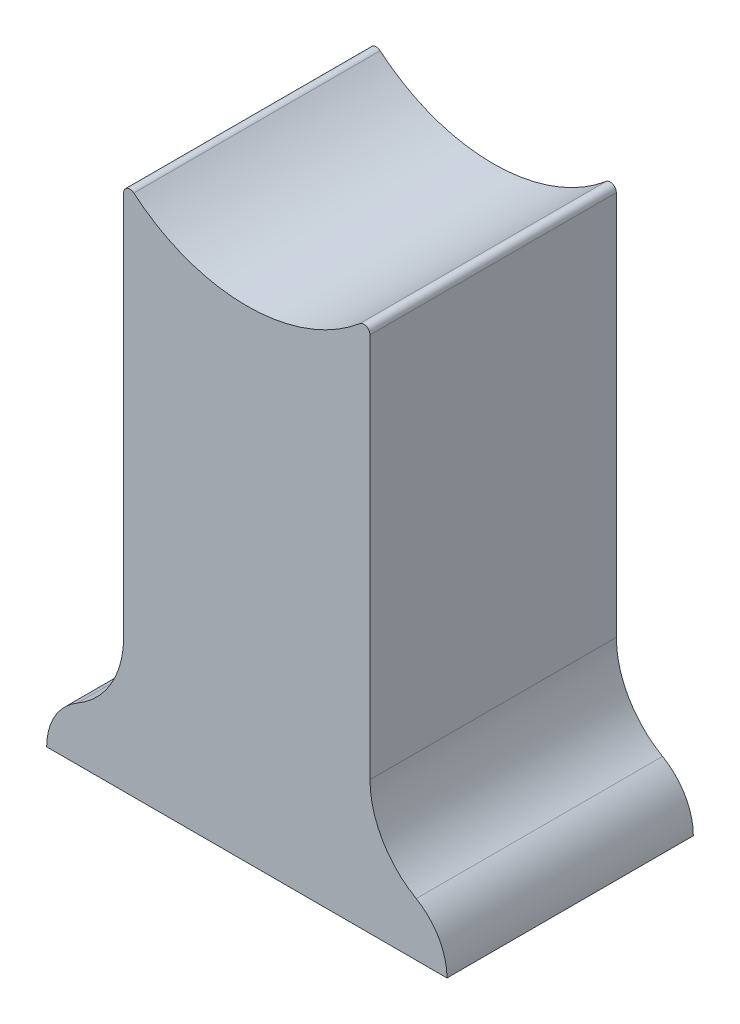
SolidWorks part; units mm, degrees
ref_plane "前视基准面" through (0, 0, 0) normal (0, 0, 1) x (1, 0, 0)
ref_plane "上视基准面" through (0, 0, 0) normal (0, 1, 0) x (1, 0, 0)
ref_plane "右视基准面" through (0, 0, 0) normal (1, 0, 0) x (0, 0, -1)
other "Configuration Table"
sketch "草图1" plane through (0, 0, 0) normal (0, 0, 1) x (1, 0, 0)
  line L0 (0, 39.5421) -> (0, -106.75) construction
  line L1 (-32.5, -106.75) -> (32.5, -106.75)
  line L4 (-20, -20.3039) -> (-20, -96.75)
  line L5 (20, -20.3039) -> (20, -96.75)
  line L6 (-32.5, -106.75) -> (-32.5, -96.75)
  line L7 (-32.5, -96.75) -> (-20, -96.75)
  line L8 (32.5, -96.75) -> (32.5, -106.75)
  line L9 (20, -96.75) -> (32.5, -96.75)
  arc A0 (-20, -20.3039) -> (20, -20.3039) centre (0, 0) ccw
  point P7 (0, 39.5421)
  dimension "D1" = 57
  dimension "D2" = 106.75
  dimension "D4" = 65
  dimension "D5" = 10
  dimension "D6" = 40
extrude "凸台-拉伸1" add sketch "草图1" along normal blind 40
fillet "圆角1" radius 1 2 edges at (20, -20.3039, 20) (-20, -20.3039, 20)
fillet "圆角2" radius 10 2 edges at (32.5, -96.75, 20) (-32.5, -96.75, 20)
fillet "圆角3" radius 15 2 edges at (20, -96.75, 20) (-20, -96.75, 20)
shell "抽壳1" thickness 4 removed face at (0, -106.75, 20)
sketch "草图3" plane through (0, -106.75, 0) normal (0, -1, 0) x (1, 0, 0)
  line L0 (-28.5, 36) -> (28.5, 36) construction
  line L1 (-2, 36) -> (2, 36)
  line L2 (-2, 36) -> (-2, 4)
  line L3 (-2, 4) -> (2, 4)
  line L4 (2, 36) -> (2, 4)
  line L5 (-28.5, 4) -> (28.5, 4) construction
  point P8 (0, 4)
  dimension "D1" = 4
extrude "凸台-拉伸2" add sketch "草图3" against normal up to surface (74.3116 mm away) up to face at (0, -30.3943, 20)
fillet "圆角4" radius 6 4 edges at (-16, -28.2887, 20) (16, -28.2887, 20) (2, -32.4384, 20) (-2, -32.4384, 20)
sketch "草图5" plane through (0, 0, 40) normal (0, 0, 1) x (1, 0, 0)
  line L3 (-32.5, -106.75) -> (32.5, -106.75)
  line L4 (20, -85.0994) -> (20, -22.5666)
  line L5 (-20, -22.5666) -> (-20, -85.0994)
  line L6 (-32.5, -106.75) -> (32.5, -106.75)
  line L7 (20, -85.0994) -> (20, -22.5666)
  line L8 (-20, -22.5666) -> (-20, -85.0994)
  arc A7 (32.5, -106.75) -> (27.5, -98.0897) centre (22.5, -106.75) ccw
  arc A8 (20, -85.0994) -> (27.5, -98.0897) centre (35, -85.0994) ccw
  arc A9 (20, -22.5666) -> (18.3559, -21.8016) centre (19, -22.5666) ccw
  arc A10 (-18.3559, -21.8016) -> (18.3559, -21.8016) centre (0, 0) ccw
  arc A11 (-18.3559, -21.8016) -> (-20, -22.5666) centre (-19, -22.5666) ccw
  arc A12 (-27.5, -98.0897) -> (-20, -85.0994) centre (-35, -85.0994) ccw
  arc A13 (-27.5, -98.0897) -> (-32.5, -106.75) centre (-22.5, -106.75) ccw
  arc A14 (32.5, -106.75) -> (27.5, -98.0897) centre (22.5, -106.75) ccw
  arc A15 (20, -85.0994) -> (27.5, -98.0897) centre (35, -85.0994) ccw
  arc A16 (20, -22.5666) -> (18.3559, -21.8016) centre (19, -22.5666) ccw
  arc A17 (-18.3559, -21.8016) -> (18.3559, -21.8016) centre (0, 0) ccw
  arc A18 (-18.3559, -21.8016) -> (-20, -22.5666) centre (-19, -22.5666) ccw
  arc A19 (-27.5, -98.0897) -> (-20, -85.0994) centre (-35, -85.0994) ccw
  arc A20 (-27.5, -98.0897) -> (-32.5, -106.75) centre (-22.5, -106.75) ccw
  dimension "D1" = 0
extrude "凸台-拉伸3" add sketch "草图5" against normal blind 2 and the other way blind 2 from offset 20 offset against normal yes
